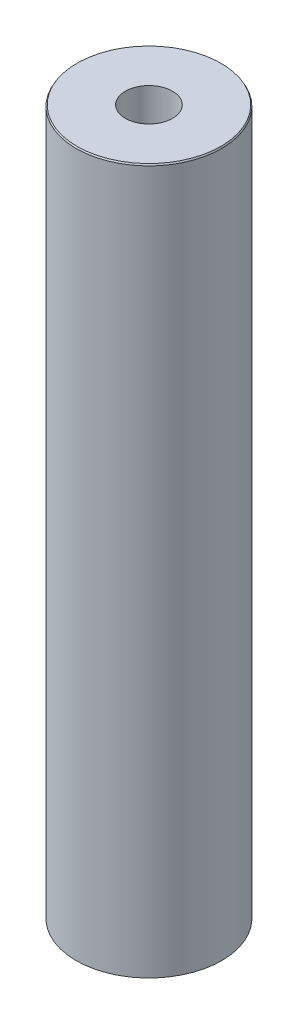
SolidWorks part; units mm, degrees
ref_plane "Front Plane" through (0, 0, 0) normal (0, 0, 1) x (1, 0, 0)
ref_plane "Top Plane" through (0, 0, 0) normal (0, 1, 0) x (1, 0, 0)
ref_plane "Right Plane" through (0, 0, 0) normal (1, 0, 0) x (0, 0, -1)
sketch "Sketch1" plane through (0, 0, 0) normal (0, 1, 0) x (1, 0, 0)
  circle A0 centre (0, 0) radius 55
  dimension "SHAFT_OD" = 110
extrude "Boss-Extrude1" add sketch "Sketch1" along normal blind 532.8556
sketch "Sketch2" plane through (0, 0, 0) normal (0, 1, 0) x (1, 0, 0)
  circle A0 centre (0, 0) radius 17.8097
  dimension "BORE_D" = 35.6193
extrude "Cut-Extrude1" cut sketch "Sketch2" along normal through all
chamfer "Chamfer1" distance 1.0927 angle 30 2 edges at (0, 532.8556, 55) (0, 0, 55) first distance on face at (0, 532.8556, 55) first distance on face at (0, 0, 17.8097)
